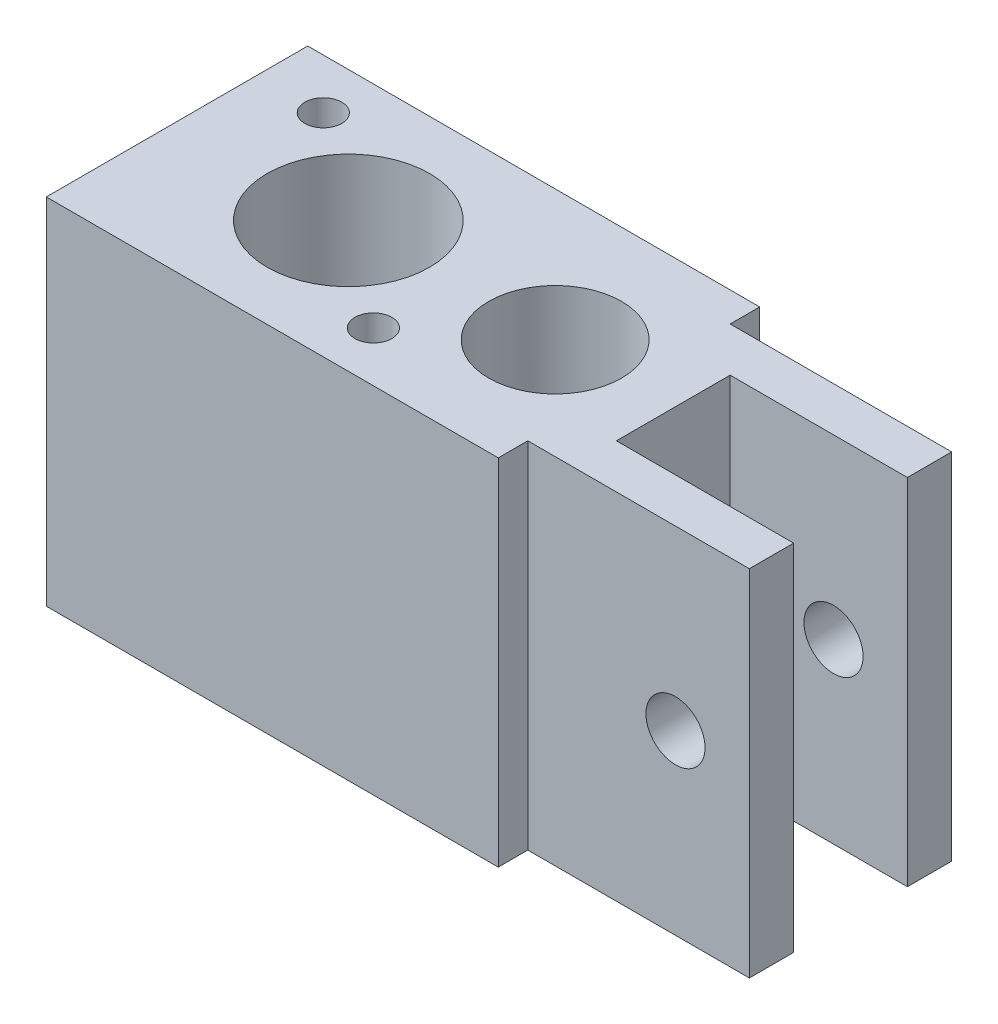
SolidWorks part; units mm, degrees
ref_plane "Ebene vorne" through (0, 0, 0) normal (0, 0, 1) x (1, 0, 0)
ref_plane "Ebene oben" through (0, 0, 0) normal (0, 1, 0) x (1, 0, 0)
ref_plane "Ebene rechts" through (0, 0, 0) normal (1, 0, 0) x (0, 0, -1)
sketch "Skizze1" plane through (0, 0, 0) normal (0, 0, 1) x (1, 0, 0)
  line L1 (-11.6, 518.1) -> (34, 518.1)
  line L2 (-11.6, 518.1) -> (-11.6, 494.1)
  line L3 (-11.6, 494.1) -> (34, 494.1)
  line L4 (34, 518.1) -> (34, 494.1)
  circle A0 centre (29, 506.1) radius 2
  point P6 (-11.6, 506.1)
sketch "Skizze2" plane through (0, 0, 0) normal (0, 1, 0) x (1, 0, 0)
  line L1 (-12.6, 8.85) -> (19, 8.85)
  line L2 (-12.6, 8.85) -> (-12.6, -8.85)
  line L3 (-12.6, 0) -> (22, 0)
  line L4 (34, 6.85) -> (34, 3.85)
  line L8 (34, 6.85) -> (19, 6.85)
  line L9 (19, 8.85) -> (19, 6.85)
  line L10 (19, -8.85) -> (19, -6.85)
  line L11 (34, -6.85) -> (19, -6.85)
  line L12 (-12.6, -8.85) -> (19, -8.85)
  line L13 (34, -3.85) -> (22, -3.85)
  line L14 (34, 3.85) -> (22, 3.85)
  line L17 (22, 3.85) -> (22, -3.85)
  line L18 (34, -3.85) -> (34, -6.85)
  circle A0 centre (14, 0) radius 4.5
  circle A1 centre (0, 0) radius 5.5
sketch "Skizze3" plane through (0, 0, 0) normal (0, 1, 0) x (1, 0, 0)
  line L0 (-12.6, -8.85) -> (-12.6, 8.85)
  line L1 (-12.6, 8.85) -> (19, 8.85)
  line L2 (19, 8.85) -> (19, 6.85)
  line L3 (19, 6.85) -> (34, 6.85)
  line L5 (-132.3655, 0) -> (132.3655, 0) construction
  line L6 (19, -6.85) -> (34, -6.85)
  line L7 (19, -8.85) -> (19, -6.85)
  line L8 (-12.6, -8.85) -> (19, -8.85)
  line L9 (34, 6.85) -> (34, 3.85)
  line L10 (22, -3.85) -> (22, 3.85)
  line L11 (22, 3.85) -> (34, 3.85)
  line L12 (-25.63, 0) -> (25.63, 0) construction
  line L13 (34, -6.85) -> (34, -3.85)
  line L14 (22, -3.85) -> (34, -3.85)
  circle A0 centre (0, 0) radius 5.5
  circle A1 centre (14, 0) radius 4.5
  point P21 (34, 0)
  point P24 (-12.6, 0)
  point P34 (22, 0)
sketch "Skizze5" plane through (0, 0, 0) normal (0, 0, 1) x (1, 0, 0)
  line L1 (-11.6, 518.1) -> (34, 518.1)
  line L2 (-11.6, 518.1) -> (-11.6, 494.1)
  line L3 (-11.6, 494.1) -> (34, 494.1)
  line L4 (34, 518.1) -> (34, 494.1)
  circle A0 centre (29, 506.1) radius 2
extrude "Aufsatz-Linear austragen1" add sketch "Skizze3" along normal up to vertex (518.1 mm away) up to point (34, 518.1, 0)
extrude "Schnitt-Linear austragen2" cut sketch "Skizze5" against normal through all both and the other way through all flip side to cut
sketch "Sketch2" plane through (0, 518.1, 0) normal (0, 1, 0) x (1, 0, 0)
  line L0 (-11.6, 8.85) -> (11.6, -8.85) construction
  line L1 (-12.6, -8.85) -> (19, -8.85) construction
  circle A0 centre (0, 0) radius 9
  circle A1 centre (-7.1553, 5.459) radius 1.25
  circle A2 centre (7.1553, -5.459) radius 1.25
  point P13 (-8.2363, 4.8313)
extrude "Cut-Extrude1" cut sketch "Sketch2" against normal blind 6 contours A2 | A1
